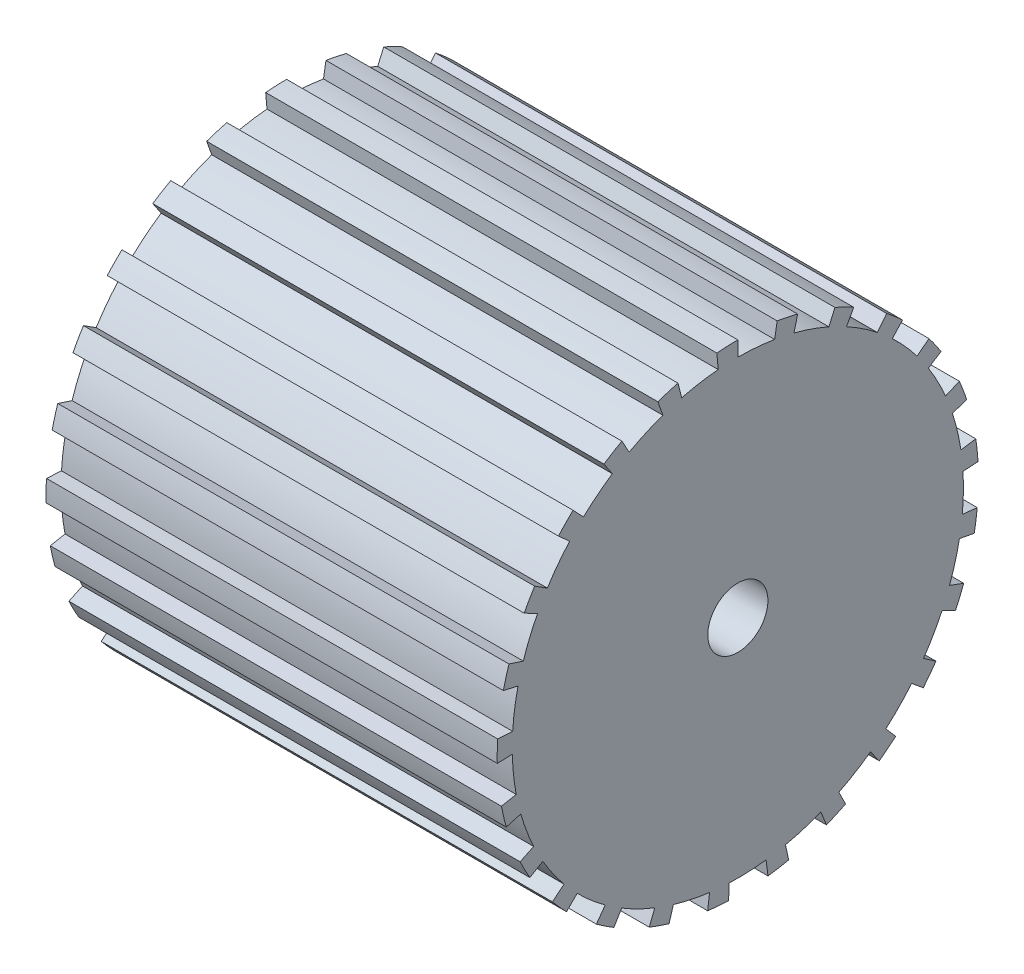
SolidWorks part; units mm, degrees
ref_plane "Front Plane" through (0, 0, 0) normal (0, 0, 1) x (1, 0, 0)
ref_plane "Top Plane" through (0, 0, 0) normal (0, 1, 0) x (1, 0, 0)
ref_plane "Right Plane" through (0, 0, 0) normal (1, 0, 0) x (0, 0, -1)
sketch "Sketch1" plane through (0, 0, 0) normal (0, 0, 1) x (1, 0, 0)
  line L0 (0, 15) -> (-30, 15)
  line L1 (0, 0) -> (-30, 0)
  line L2 (0, 0) -> (0, 15)
  line L4 (-30, 0) -> (-30, 15)
  dimension "D1" = 15
  dimension "D2" = 30
revolve "Revolve1" add sketch "Sketch1" angle 360 about L1
sketch "Sketch2" plane through (-30, 0, 0) normal (-1, 0, 0) x (0, 0, 1)
  circle A0 centre (0, 0) radius 2
  dimension "D1" = 4
extrude "Cut-Extrude1" cut sketch "Sketch2" against normal through all
sketch "Sketch3" plane through (-30, 0, 0) normal (-1, 0, 0) x (0, 0, 1)
  line L0 (0, 2) -> (0, 16)
  line L1 (0.1743, 1.9924) -> (1.3945, 15.9391)
  line L2 (0, 0) -> (0.1743, 1.9924) construction
  line L3 (0, 0) -> (0, 2) construction
  line L4 (0.4974, 1.9372) -> (3.979, 15.4973)
  line L5 (0.6643, 1.8864) -> (5.3146, 15.0916)
  line L6 (0.9635, 1.7526) -> (7.7081, 14.0209)
  line L7 (1.1126, 1.662) -> (8.9007, 13.2958)
  line L8 (1.3691, 1.4579) -> (10.9528, 11.6635)
  line L9 (1.491, 1.3331) -> (11.9276, 10.6645)
  line L10 (1.6887, 1.0717) -> (13.5092, 8.5732)
  line L11 (1.7756, 0.9204) -> (14.205, 7.3632)
  line L12 (1.9021, 0.618) -> (15.2169, 4.9443)
  line L13 (1.9487, 0.4499) -> (15.5899, 3.5992)
  line L14 (1.9961, 0.1256) -> (15.9684, 1.0046)
  line L15 (1.9994, -0.0489) -> (15.9952, -0.3909)
  line L16 (1.9646, -0.3748) -> (15.7166, -2.9981)
  line L17 (1.9244, -0.5446) -> (15.3955, -4.3565)
  line L18 (1.8097, -0.8516) -> (14.4772, -6.8125)
  line L19 (1.7285, -1.006) -> (13.8284, -8.0483)
  line L20 (1.541, -1.2748) -> (12.3282, -10.1988)
  line L21 (1.4241, -1.4043) -> (11.3924, -11.2344)
  line L22 (1.1756, -1.618) -> (9.4046, -12.9443)
  line L23 (1.0301, -1.7143) -> (8.2406, -13.7147)
  line L24 (0.7362, -1.8596) -> (5.89, -14.8764)
  line L25 (0.5714, -1.9166) -> (4.571, -15.3332)
  line L26 (0.2507, -1.9842) -> (2.0053, -15.8738)
  line L27 (0.0768, -1.9985) -> (0.6142, -15.9882)
  line L28 (-0.2507, -1.9842) -> (-2.0053, -15.8738)
  line L29 (-0.4226, -1.9548) -> (-3.3812, -15.6387)
  line L30 (-0.7362, -1.8596) -> (-5.89, -14.8764)
  line L31 (-0.8955, -1.7883) -> (-7.1641, -14.3065)
  line L32 (-1.1756, -1.618) -> (-9.4046, -12.9443)
  line L33 (-1.3121, -1.5094) -> (-10.4969, -12.0754)
  line L34 (-1.541, -1.2748) -> (-12.3282, -10.1988)
  line L35 (-1.6463, -1.1357) -> (-13.1702, -9.0855)
  line L36 (-1.8097, -0.8516) -> (-14.4772, -6.8125)
  line L37 (-1.877, -0.6906) -> (-15.0159, -5.5248)
  line L38 (-1.9646, -0.3748) -> (-15.7166, -2.9981)
  line L39 (-1.9898, -0.2021) -> (-15.9181, -1.6169)
  line L40 (-1.9961, 0.1256) -> (-15.9684, 1.0046)
  line L41 (-1.9775, 0.2991) -> (-15.8201, 2.3926)
  line L42 (-1.9021, 0.618) -> (-15.2169, 4.9443)
  line L43 (-1.841, 0.7815) -> (-14.7281, 6.2517)
  line L44 (-1.6887, 1.0717) -> (-13.5092, 8.5732)
  line L45 (-1.5888, 1.2148) -> (-12.7106, 9.718)
  line L46 (-1.3691, 1.4579) -> (-10.9528, 11.6635)
  line L47 (-1.2368, 1.5717) -> (-9.8945, 12.5737)
  line L48 (-0.9635, 1.7526) -> (-7.7081, 14.0209)
  line L49 (-0.8071, 1.8299) -> (-6.4567, 14.6394)
  line L50 (-0.4974, 1.9372) -> (-3.979, 15.4973)
  line L51 (-0.3267, 1.9731) -> (-2.6132, 15.7852)
  arc A0 (1.3945, 15.9391) -> (0, 16) centre (0, 0) ccw
  arc A1 (0, 16) -> (1.3945, 15.9391) centre (0, 0) ccw construction
  arc A2 (0.1743, 1.9924) -> (0, 2) centre (0, 0) ccw
  arc A3 (0, 2) -> (0.1743, 1.9924) centre (0, 0) ccw construction
  arc A4 (0.6643, 1.8864) -> (0.4974, 1.9372) centre (0, 0) ccw
  arc A5 (5.3146, 15.0916) -> (3.979, 15.4973) centre (0, 0) ccw
  arc A6 (1.1126, 1.662) -> (0.9635, 1.7526) centre (0, 0) ccw
  arc A7 (8.9007, 13.2958) -> (7.7081, 14.0209) centre (0, 0) ccw
  arc A8 (1.491, 1.3331) -> (1.3691, 1.4579) centre (0, 0) ccw
  arc A9 (11.9276, 10.6645) -> (10.9528, 11.6635) centre (0, 0) ccw
  arc A10 (1.7756, 0.9204) -> (1.6887, 1.0717) centre (0, 0) ccw
  arc A11 (14.205, 7.3632) -> (13.5092, 8.5732) centre (0, 0) ccw
  arc A12 (1.9487, 0.4499) -> (1.9021, 0.618) centre (0, 0) ccw
  arc A13 (15.5899, 3.5992) -> (15.2169, 4.9443) centre (0, 0) ccw
  arc A14 (1.9994, -0.0489) -> (1.9961, 0.1256) centre (0, 0) ccw
  arc A15 (15.9952, -0.3909) -> (15.9684, 1.0046) centre (0, 0) ccw
  arc A16 (1.9244, -0.5446) -> (1.9646, -0.3748) centre (0, 0) ccw
  arc A17 (15.3955, -4.3565) -> (15.7166, -2.9981) centre (0, 0) ccw
  arc A18 (1.7285, -1.006) -> (1.8097, -0.8516) centre (0, 0) ccw
  arc A19 (13.8284, -8.0483) -> (14.4772, -6.8125) centre (0, 0) ccw
  arc A20 (1.4241, -1.4043) -> (1.541, -1.2748) centre (0, 0) ccw
  arc A21 (11.3924, -11.2344) -> (12.3282, -10.1988) centre (0, 0) ccw
  arc A22 (1.0301, -1.7143) -> (1.1756, -1.618) centre (0, 0) ccw
  arc A23 (8.2406, -13.7147) -> (9.4046, -12.9443) centre (0, 0) ccw
  arc A24 (0.5714, -1.9166) -> (0.7362, -1.8596) centre (0, 0) ccw
  arc A25 (4.571, -15.3332) -> (5.89, -14.8764) centre (0, 0) ccw
  arc A26 (0.0768, -1.9985) -> (0.2507, -1.9842) centre (0, 0) ccw
  arc A27 (0.6142, -15.9882) -> (2.0053, -15.8738) centre (0, 0) ccw
  arc A28 (-0.4226, -1.9548) -> (-0.2507, -1.9842) centre (0, 0) ccw
  arc A29 (-3.3812, -15.6387) -> (-2.0053, -15.8738) centre (0, 0) ccw
  arc A30 (-0.8955, -1.7883) -> (-0.7362, -1.8596) centre (0, 0) ccw
  arc A31 (-7.1641, -14.3065) -> (-5.89, -14.8764) centre (0, 0) ccw
  arc A32 (-1.3121, -1.5094) -> (-1.1756, -1.618) centre (0, 0) ccw
  arc A33 (-10.4969, -12.0754) -> (-9.4046, -12.9443) centre (0, 0) ccw
  arc A34 (-1.6463, -1.1357) -> (-1.541, -1.2748) centre (0, 0) ccw
  arc A35 (-13.1702, -9.0855) -> (-12.3282, -10.1988) centre (0, 0) ccw
  arc A36 (-1.877, -0.6906) -> (-1.8097, -0.8516) centre (0, 0) ccw
  arc A37 (-15.0159, -5.5248) -> (-14.4772, -6.8125) centre (0, 0) ccw
  arc A38 (-1.9898, -0.2021) -> (-1.9646, -0.3748) centre (0, 0) ccw
  arc A39 (-15.9181, -1.6169) -> (-15.7166, -2.9981) centre (0, 0) ccw
  arc A40 (-1.9775, 0.2991) -> (-1.9961, 0.1256) centre (0, 0) ccw
  arc A41 (-15.8201, 2.3926) -> (-15.9684, 1.0046) centre (0, 0) ccw
  arc A42 (-1.841, 0.7815) -> (-1.9021, 0.618) centre (0, 0) ccw
  arc A43 (-14.7281, 6.2517) -> (-15.2169, 4.9443) centre (0, 0) ccw
  arc A44 (-1.5888, 1.2148) -> (-1.6887, 1.0717) centre (0, 0) ccw
  arc A45 (-12.7106, 9.718) -> (-13.5092, 8.5732) centre (0, 0) ccw
  arc A46 (-1.2368, 1.5717) -> (-1.3691, 1.4579) centre (0, 0) ccw
  arc A47 (-9.8945, 12.5737) -> (-10.9528, 11.6635) centre (0, 0) ccw
  arc A48 (-0.8071, 1.8299) -> (-0.9635, 1.7526) centre (0, 0) ccw
  arc A49 (-6.4567, 14.6394) -> (-7.7081, 14.0209) centre (0, 0) ccw
  arc A50 (-0.3267, 1.9731) -> (-0.4974, 1.9372) centre (0, 0) ccw
  arc A51 (-2.6132, 15.7852) -> (-3.979, 15.4973) centre (0, 0) ccw
  circle A53 centre (0, 0) radius 15 construction
  point P105 (0, 0)
  dimension "D1" = 1
  dimension "D3" = 4
  dimension "D2" = 5
  dimension "D4" = 25
extrude "Boss-Extrude1" add sketch "Sketch3" against normal up to surface (30 mm away) up to face at (0, -2, 0)
